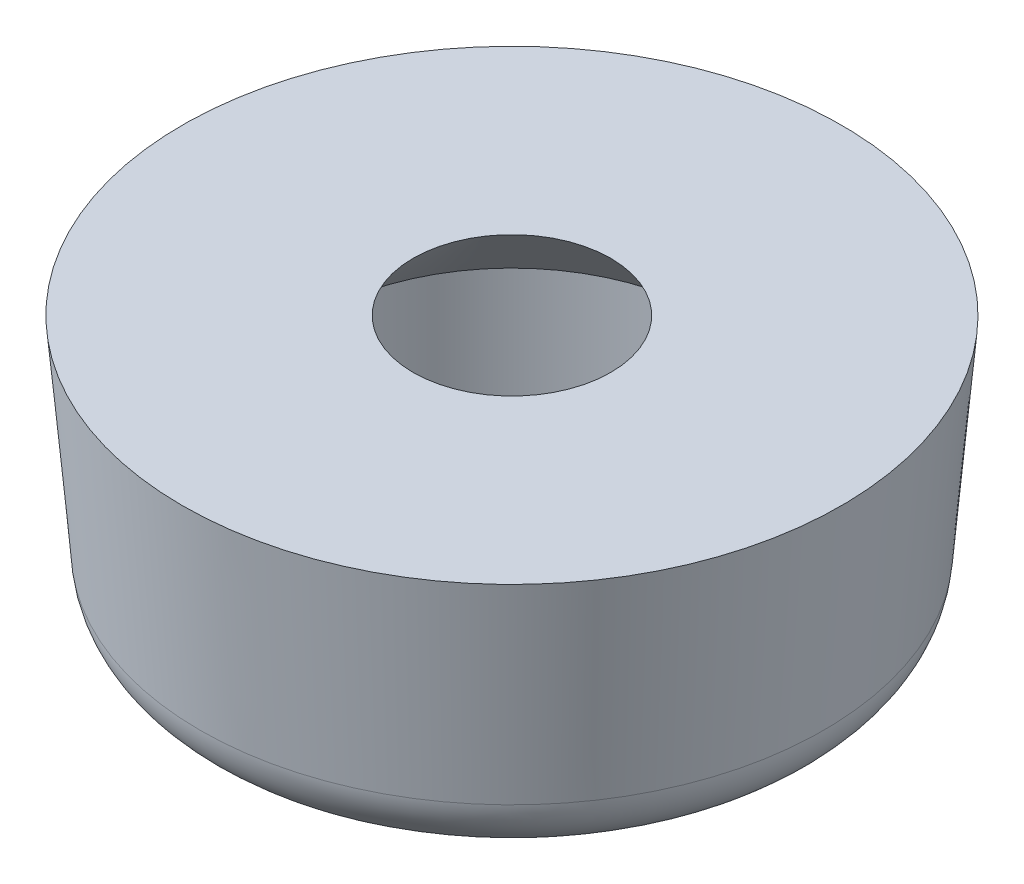
SolidWorks part; units mm, degrees
ref_plane "Спереди" through (0, 0, 0) normal (0, 0, 1) x (1, 0, 0)
ref_plane "Сверху" through (0, 0, 0) normal (0, 1, 0) x (1, 0, 0)
ref_plane "Справа" through (0, 0, 0) normal (1, 0, 0) x (0, 0, -1)
sketch "Эскиз1" plane through (0, 0, 0) normal (0, 1, 0) x (1, 0, 0)
  circle A0 centre (0, 0) radius 5
extrude "Бобышка-Вытянуть1" add sketch "Эскиз1" along normal blind 4
sketch "Эскиз2" plane through (0, 4, 0) normal (0, 1, 0) x (1, 0, 0)
  circle A0 centre (0, 0) radius 1.5
extrude "Вырез-Вытянуть1" cut sketch "Эскиз2" against normal blind 5
draft "Уклон1" type of draft neutral plane draft angle 1 faces to draft 1 face at (0, 4, 5) neutral plane through (0, 4, 0) neutral plane normal (0, 1, 0) reverse direction yes parameters "D1"=1
draft "Уклон4" type of draft neutral plane draft angle 5 faces to draft 1 face at (0, 4, 5) neutral plane through (0, 4, 0) neutral plane normal (0, 1, 0) reverse direction yes parameters "D1"=5
sketch "Эскиз3" plane through (0, 0, 0) normal (0, -1, 0) x (1, 0, 0)
  circle A0 centre (0, 0) radius 3
extrude "Вырез-Вытянуть2" cut sketch "Эскиз3" against normal blind 2
fillet "Скругление1" radius 1 1 edges at (0, 0, 4.65)
chamfer "Фаска1" distance 2 angle 45 1 edges at (0, 2, -1.5)
